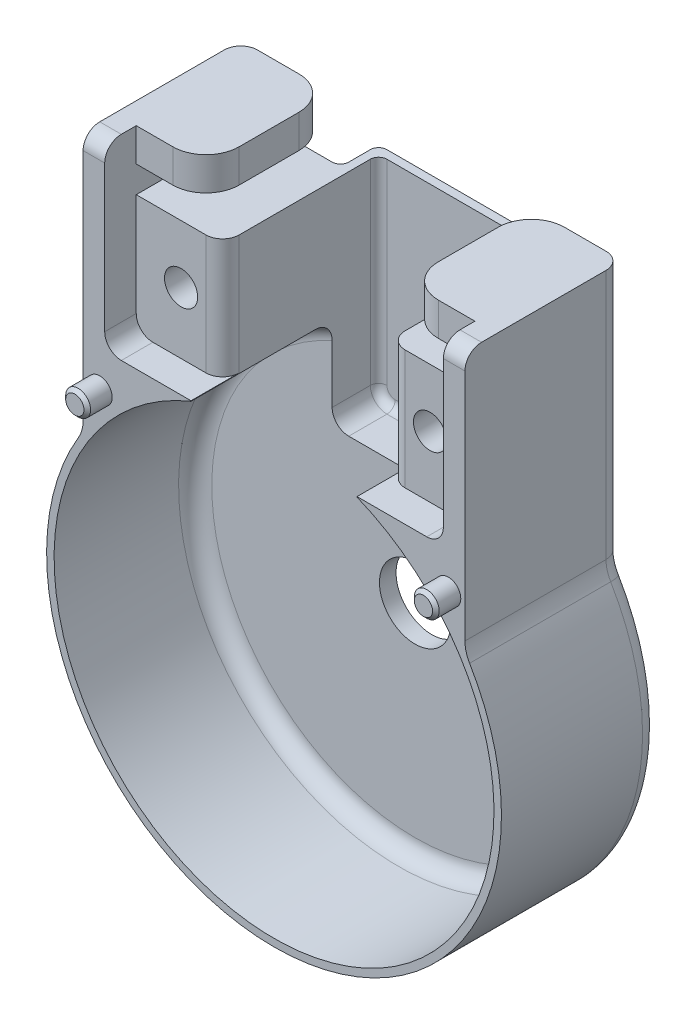
SolidWorks part; units mm, degrees
material "ABS PC"
ref_plane "前视基准面" through (0, 0, 0) normal (0, 0, 1) x (1, 0, 0)
ref_plane "上视基准面" through (0, 0, 0) normal (0, 1, 0) x (1, 0, 0)
ref_plane "右视基准面" through (0, 0, 0) normal (1, 0, 0) x (0, 0, -1)
sketch "草图1" plane through (0, 0, 0) normal (0, 0, 1) x (1, 0, 0)
  line L0 (-13.7, 0) -> (-13.7, 19.5)
  line L1 (-13.7, 19.5) -> (13.7, 19.5)
  line L2 (13.7, 19.5) -> (13.7, 0)
  circle A0 centre (0, 0) radius 13.7 construction
  arc A1 (-13.7, 0) -> (13.7, 0) centre (0, 0) ccw
  dimension "D1" = 27.4
  dimension "D2" = 19.5
extrude "凸台-拉伸1" add sketch "草图1" along normal blind 9.5
sketch "草图2" plane through (0, 0, 9.5) normal (0, 0, 1) x (1, 0, 0)
  circle A0 centre (0, 0) radius 13.25
  dimension "D1" = 26.5
extrude "切除-拉伸1" cut sketch "草图2" against normal offset from surface (8.5 mm away) 1 up to face at (0, 6.325, 0)
sketch "草图3" plane through (0, 0, 9.5) normal (0, 0, 1) x (1, 0, 0)
  line L0 (13.7, 19.5) -> (-13.7, 19.5) construction
  line L1 (5, 32.3) -> (-5, 32.3)
  line L2 (5, 32.3) -> (5, 6.7)
  line L3 (5, 6.7) -> (-5, 6.7)
  line L4 (-5, 32.3) -> (-5, 6.7)
  line L5 (5, 32.3) -> (-5, 6.7) construction
  line L6 (5, 6.7) -> (-5, 32.3) construction
  point P0 (0, 19.5)
  dimension "D1" = 10
  dimension "D2" = 12.8
extrude "切除-拉伸2" cut sketch "草图3" against normal blind 27
sketch "草图8" plane through (0, 0, 1) normal (0, 0, 1) x (1, 0, 0)
  circle A0 centre (0, 0) radius 2.15
  dimension "D1" = 4.3
extrude "切除-拉伸5" cut sketch "草图8" against normal blind 10
sketch "草图9" plane through (0, 0, 9.5) normal (0, 0, 1) x (1, 0, 0)
  line L0 (0, 0) -> (0, 26.9482) construction
  line L2 (10.2, 26.2414) -> (-10.2, 26.2414)
  line L3 (10.2, 26.2414) -> (10.2, 12.3)
  line L4 (10.2, 12.3) -> (-10.2, 12.3)
  line L5 (-10.2, 26.2414) -> (-10.2, 12.3)
  line L6 (10.2, 26.2414) -> (-10.2, 12.3) construction
  line L7 (10.2, 12.3) -> (-10.2, 26.2414) construction
  line L8 (-5, 19.5) -> (-13.7, 19.5) construction
  point P3 (0, 19.2707)
  dimension "D1" = 7.2
  dimension "D2" = 20.4
extrude "切除-拉伸6" cut sketch "草图9" against normal blind 1.9
sketch "草图10" plane through (0, 0, 0) normal (0, 0, -1) x (-1, 0, 0)
  line L0 (-13.7, 19.5) -> (-5, 19.5) construction
  line L1 (7.5, -16) -> (-7.5, -16) construction
  line L2 (7.5, -16) -> (7.5, 16) construction
  line L3 (7.5, 16) -> (-7.5, 16) construction
  line L4 (-7.5, -16) -> (-7.5, 16) construction
  line L5 (7.5, -16) -> (-7.5, 16) construction
  line L6 (7.5, 16) -> (-7.5, -16) construction
  circle A0 centre (-7.5, 16) radius 2
  circle A1 centre (7.5, 16) radius 2
  point P0 (0, 0)
  dimension "D3" = 4
  dimension "D4" = 4
  dimension "D1" = 15
  dimension "D2" = 3.5
extrude "切除-拉伸7" cut sketch "草图10" against normal offset from surface (5.6 mm away) 2 up to face at (7.6, 15.9, 7.6)
fillet "圆角8" radius 1 2 edges at (10.2, 12.3, 8.55) (-10.2, 12.3, 8.55)
sketch "草图17" plane through (0, 19.5, 0) normal (0, 1, 0) x (1, 0, 0)
  line L0 (0, 3.35) -> (0, -13.0876) construction
  line L1 (5, -7.6) -> (5, 0)
  line L2 (10.2, -7.6) -> (5, -7.6)
  line L3 (10.2, -9.5) -> (10.2, -7.6)
  line L4 (13.7, -9.5) -> (10.2, -9.5)
  line L5 (13.7, 0) -> (13.7, -9.5)
  line L6 (-5, 0) -> (-13.7, 0)
  line L7 (-5, 0) -> (-13.7, 0)
  line L8 (5, 0) -> (13.7, 0)
  line L13 (-13.7, 0) -> (-13.7, -9.5)
  line L14 (-13.7, -9.5) -> (-10.2, -9.5)
  line L15 (-10.2, -9.5) -> (-10.2, -7.6)
  line L16 (-10.2, -7.6) -> (-5, -7.6)
  line L17 (-5, -7.6) -> (-5, 0)
  line L25 (-13.7, 0) -> (-13.7, -9.5)
  line L26 (-13.7, -9.5) -> (-10.2, -9.5)
  line L27 (-10.2, -9.5) -> (-10.2, -7.6)
  line L28 (-10.2, -7.6) -> (-5, -7.6)
  line L29 (-5, -7.6) -> (-5, 0)
  dimension "D1" = 0
extrude "凸台-拉伸4" add sketch "草图17" along normal blind 3.6
sketch "草图18" plane through (0, 0, 9.5) normal (0, 0, 1) x (1, 0, 0)
  line L3 (10.2, 19.5) -> (-10.2, 19.5)
  line L4 (10.2, 19.5) -> (10.2, 21.1)
  line L5 (10.2, 21.1) -> (-10.2, 21.1)
  line L6 (-10.2, 19.5) -> (-10.2, 21.1)
  line L7 (10.2, 19.5) -> (-10.2, 21.1) construction
  line L8 (10.2, 21.1) -> (-10.2, 19.5) construction
  line L9 (-10.2, 23.1) -> (-10.2, 13.3) construction
  dimension "D1" = 19.5
  dimension "D2" = 1.6
  dimension "D3" = 20.4
extrude "切除-拉伸10" cut sketch "草图18" against normal blind 23.6
sketch "草图21" plane through (0, 0, 9.5) normal (0, 0, 1) x (1, 0, 0)
  line L1 (-5, 19.5) -> (-10.2, 19.5) construction
  line L2 (-5, 19.5) -> (-5, 12.3) construction
  circle A0 centre (-10.5, 10.1) radius 0.75
  dimension "D1" = 5.5
  dimension "D2" = 9.4
  dimension "D3" = 1.5
extrude "凸台-拉伸6" add sketch "草图21" along normal blind 1.5
mirror "镜向1" about plane through (0, 0, 0) normal (1, 0, 0) of "凸台-拉伸6"
chamfer "倒角3" distance 0.2 angle 45 2 edges at (9.75, 10.1, 11) (-9.75, 10.1, 11)
sketch "草图22" plane through (0, 23.1, 0) normal (0, 1, 0) x (1, 0, 0)
  line L1 (6, 13.3591) -> (-6, 13.3591)
  line L2 (6, 13.3591) -> (6, -13.3591)
  line L3 (6, -13.3591) -> (-6, -13.3591)
  line L4 (-6, 13.3591) -> (-6, -13.3591)
  line L5 (6, 13.3591) -> (-6, -13.3591) construction
  line L6 (6, -13.3591) -> (-6, 13.3591) construction
  point P0 (0, 0)
  dimension "D1" = 12
extrude "切除-拉伸12" cut sketch "草图22" against normal up to surface (2 mm away) up to face at (-7.6, 21.1, 3.8)
fillet "圆角9" radius 2 4 edges at (-6, 22.1, 0) (-6, 22.1, 7.6) (6, 22.1, 0) (6, 22.1, 7.6)
sketch "草图23" plane through (0, 0, 0) normal (0, 0, -1) x (-1, 0, 0)
  line L0 (-11.5, 26.537) -> (-11.5, 7.4458)
  line L4 (-11.5, 26.537) -> (-15.4065, 26.537)
  line L5 (-13.7, 0) -> (-15.4065, 0)
  line L6 (-15.4065, 0) -> (-15.4065, 26.537)
  arc A0 (-13.7, 0) -> (-11.5, 7.4458) centre (0, 0) cw
  circle A1 centre (-7.5, 16) radius 2 construction
  dimension "D1" = 4
  dimension "D2" = 13.7
extrude "切除-拉伸13" cut sketch "草图23" against normal blind 27
mirror "镜向2" about plane through (0, 0, 0) normal (1, 0, 0) of "切除-拉伸13"
sketch "草图24" plane through (0, 0, 0) normal (0, 0, -1) x (-1, 0, 0)
  line L0 (-5.5, 19.5) -> (-5.5, 6.2)
  line L1 (-5, 19.5) -> (5, 19.5) construction
  line L2 (-5, 19.5) -> (-5, 6.7)
  line L3 (-5, 6.7) -> (5, 6.7)
  line L4 (5, 19.5) -> (5, 6.7)
  line L5 (-5.5, 19.5) -> (5.5, 19.5) construction
  line L6 (5.5, 19.5) -> (5.5, 6.2)
  line L7 (-5.5, 6.2) -> (5.5, 6.2)
  line L11 (-5, 19.5) -> (-5.5, 19.5)
  line L12 (5, 19.5) -> (5.5, 19.5)
  line L13 (-5, 19.5) -> (-10.2, 19.5) construction
  line L14 (-5, 6.7) -> (-5, 19.5) construction
  dimension "D1" = 0.5
  dimension "D2" = 0.5
extrude "凸台-拉伸7" add sketch "草图24" along normal blind 1.8
sketch "草图25" plane through (0, 0, -1.8) normal (0, 0, -1) x (-1, 0, 0)
  line L1 (-5.5, 19.5) -> (5.5, 19.5)
  line L2 (-5.5, 19.5) -> (-5.5, 6.2)
  line L3 (-5.5, 6.2) -> (5.5, 6.2)
  line L4 (5.5, 19.5) -> (5.5, 6.2)
extrude "凸台-拉伸8" add sketch "草图25" along normal blind 0.5
fillet "圆角10" radius 1 4 edges at (5, 6.7, -0.4) (-5, 6.7, -0.4) (-5.5, 6.2, -1.15) (5.5, 6.2, -1.15)
sketch "草图27" plane through (0, 0, 9.5) normal (0, 0, 1) x (1, 0, 0)
  line L0 (0, 0) -> (0, 32.1569) construction
  line L2 (9.2, 37.7371) -> (-9.2, 37.7371)
  line L3 (9.2, 37.7371) -> (9.2, 5.5601)
  line L4 (9.2, 5.5601) -> (-9.2, 5.5601)
  line L5 (-9.2, 37.7371) -> (-9.2, 5.5601)
  line L6 (9.2, 37.7371) -> (-9.2, 5.5601) construction
  line L7 (9.2, 5.5601) -> (-9.2, 37.7371) construction
  point P2 (0, 21.6486)
  dimension "D1" = 18.4
extrude "切除-拉伸14" [suppressed] cut sketch "草图27" against normal up to surface (1.9 mm away)
fillet "圆角11" radius 2 2 edges at (11.5, 7.4458, 4.75) (-11.5, 7.4458, 4.75)
fillet "圆角12" radius 1 6 edges at (-11.5, 15.5575, 0) (-11.5713, 7.4856, 0) (0, -13.7, 0) (11.5713, 7.4856, 0) (0, -13.25, 1) (11.5, 15.5575, 0)
fillet "圆角13" radius 1 2 edges at (5, 15.9, 7.6) (-5, 15.9, 7.6)
fillet "圆角14" radius 0.5 12 edges at (0, 6.2, 0) (5.5, 17.75, 0) (5.5, 11.6, 0) (-5.5, 17.75, 0) (-5.5, 11.6, 0) (-5.2071, 6.4929, -2.3) (5.2071, 6.4929, -2.3) (-5.2071, 6.4929, 0) (5.2071, 6.4929, 0) (5.5, 13.35, -2.3) (-5.5, 13.35, -2.3) (0, 6.2, -2.3)
fillet "圆角15" radius 0.5 5 edges at (4.7071, 6.9929, -1.8) (0, 6.7, -1.8) (-4.7071, 6.9929, -1.8)
fillet "圆角16" radius 1 2 edges at (10.85, 23.1, 9.5) (-10.85, 23.1, 9.5)
sketch "草图28" plane through (0, 0, 5.6) normal (0, 0, -1) x (-1, 0, 0)
  circle A0 centre (-7.5, 16) radius 1
  circle A1 centre (7.5, 16) radius 1
  dimension "D1" = 2
  dimension "D2" = 2
extrude "切除-拉伸15" cut sketch "草图28" against normal blind 10
